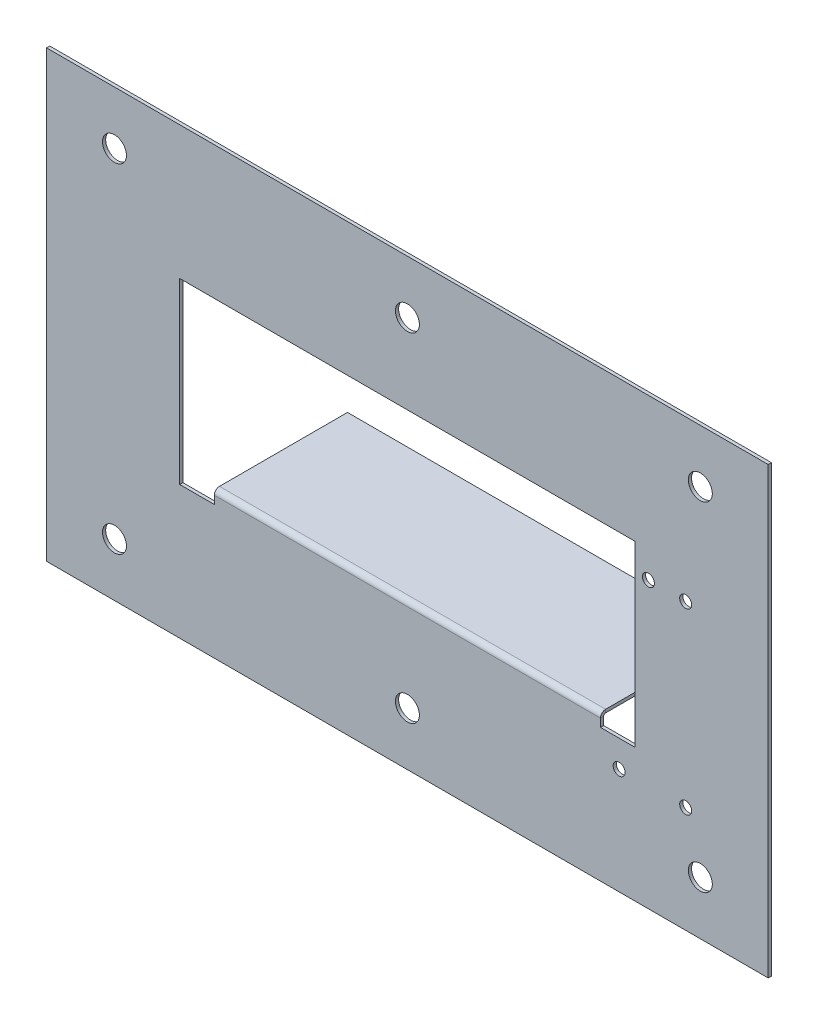
SolidWorks part; units mm, degrees
note: The reader was unsure of these and kept them because the rebuilt part matched: flange length of "Ребро-кромка1".
ref_plane "Спереди" through (0, 0, 0) normal (0, 0, 1) x (1, 0, 0)
ref_plane "Сверху" through (0, 0, 0) normal (0, 1, 0) x (1, 0, 0)
ref_plane "Справа" through (0, 0, 0) normal (1, 0, 0) x (0, 0, -1)
sketch "Эскиз1" plane through (0, 0, 0) normal (0, 0, 1) x (1, 0, 0)
  line L0 (190, 53.9366) -> (176, 53.9366) construction
  line L1 (13, 0) -> (158, 0)
  line L2 (0, 0) -> (0, 64)
  line L3 (0, 64) -> (171, 64)
  line L4 (171, 0) -> (171, 64)
  line L5 (-50, 114) -> (221, 114)
  line L6 (-50, 114) -> (-50, -53)
  line L7 (-50, -53) -> (221, -53)
  line L8 (221, 114) -> (221, -53)
  line L9 (176, 53.9366) -> (190, -13.0634) construction
  line L10 (0, 0) -> (0, -3)
  line L11 (0, -3) -> (13, -3)
  line L12 (13, 0) -> (13, -3)
  line L13 (190, -13.0634) -> (165, -13.0634) construction
  line L14 (171, 0) -> (171, -3)
  line L15 (171, -3) -> (158, -3)
  line L16 (158, 0) -> (158, -3)
  circle A0 centre (176, 53.9366) radius 2.25
  circle A1 centre (190, 53.9366) radius 2.25
  circle A2 centre (165, -13.0634) radius 2.25
  circle A3 centre (190, -13.0634) radius 2.25
  dimension "D17" = 4.5
  dimension "D1" = 64
  dimension "D2" = 171
  dimension "D3" = 13
  dimension "D4" = 3
  dimension "D5" = 3
  dimension "D6" = 13
  dimension "D7" = 50
  dimension "D8" = 50
  dimension "D9" = 50
  dimension "D10" = 50
  dimension "D11" = 14
  dimension "D12" = 60.0634
  dimension "D13" = 31
  dimension "D14" = 39.9366
  dimension "D15" = 25
  dimension "D16" = 31
base flange "Базовая кромка1" sketch "Эскиз1" thickness 1.2 reverse thickness direction no parameters "D1"=0.7366
edge flange "Ребро-кромка1" sketch "Эскиз8" flange angle 90 flange length 50 flange position bend outside bend radius 0.7366 thickness 1.2 relief rectangular parameters "D6"=10
sketch "Эскиз8" plane through (0, 0, -1.2) normal (0, 1, 0) x (1, 0, 0)
  line L0 (13, 0) -> (158, 0) construction
  line L1 (13, 0) -> (158, 0)
  line L2 (13, 0) -> (13, 48.8)
  line L3 (13, 48.8) -> (158, 48.8)
  line L4 (158, 48.8) -> (158, 0)
bend "EdgeBend1" bend radius 0.7366 bend angle 90 parameters "D5"=1
sketch "Эскиз9" plane through (0, 0, 0) normal (0, 0, 1) x (1, 0, 0)
  line L0 (-50, 94) -> (221, 94) construction
  line L1 (-50, 114) -> (-50, -53) construction
  line L2 (221, -53) -> (221, 114) construction
  line L3 (221, 94) -> (-50, -33) construction
  line L4 (-50, -33) -> (221, -33) construction
  line L5 (221, 114) -> (-50, 114) construction
  line L6 (-50, -53) -> (221, -53) construction
  line L7 (-24.5, -33) -> (-24.5, 94) construction
  line L8 (-24.5, 94) -> (85.5, -33) construction
  line L9 (85.5, -33) -> (85.5, 94) construction
  line L10 (85.5, 94) -> (195.5, -33) construction
  line L11 (195.5, -33) -> (195.5, 94) construction
  circle A0 centre (-24.5, 94) radius 4.5
  circle A1 centre (-24.5, -33) radius 4.5
  circle A2 centre (85.5, -33) radius 4.5
  circle A3 centre (85.5, 94) radius 4.5
  circle A4 centre (195.5, 94) radius 4.5
  circle A5 centre (195.5, -33) radius 4.5
  dimension "D3" = 9
  dimension "D1" = 20
  dimension "D2" = 20
  dimension "D4" = 220
extrude "Вырез-Вытянуть1" cut sketch "Эскиз9" against normal up to next normal cut yes
sketch "Сгиб-Линии1" plane through (0, 0, 0) normal (0, 1, 0) x (1, 0, 0)
sketch "Граничная рамка1" plane through (0, 0, 0) normal (0, 1, 0) x (1, 0, 0)
sheet metal parameters "Листовой металл3" thickness 1.2 parameters "D1"=0.7366
flat pattern "Развертка3" [suppressed]
sketch "Сгиб-Линии2" plane through (0, 0, 0) normal (0, 1, 0) x (1, 0, 0)
sketch "Граничная рамка2" [suppressed] plane through (0, 0, 0) normal (0, 1, 0) x (1, 0, 0)
sheet metal parameters "Листовой металл4" thickness 1.2 parameters "D1"=0.7366
flat pattern "Развертка3" [suppressed]
sketch "Сгиб-Линии2" plane through (0, 0, 0) normal (0, 1, 0) x (1, 0, 0)
sketch "Граничная рамка2" [suppressed] plane through (0, 0, 0) normal (0, 1, 0) x (1, 0, 0)
bend of the flat pattern "Плоское состояние-<EdgeBend1>1"
sheet metal parameters "Листовой металл5" thickness 1.2 parameters "D1"=0.7366
flat pattern "Развертка3" [suppressed]
sketch "Сгиб-Линии2" plane through (0, 0, 0) normal (0, 1, 0) x (1, 0, 0)
sketch "Граничная рамка2" [suppressed] plane through (0, 0, 0) normal (0, 1, 0) x (1, 0, 0)
bend of the flat pattern "Плоское состояние-<EdgeBend1>1"
